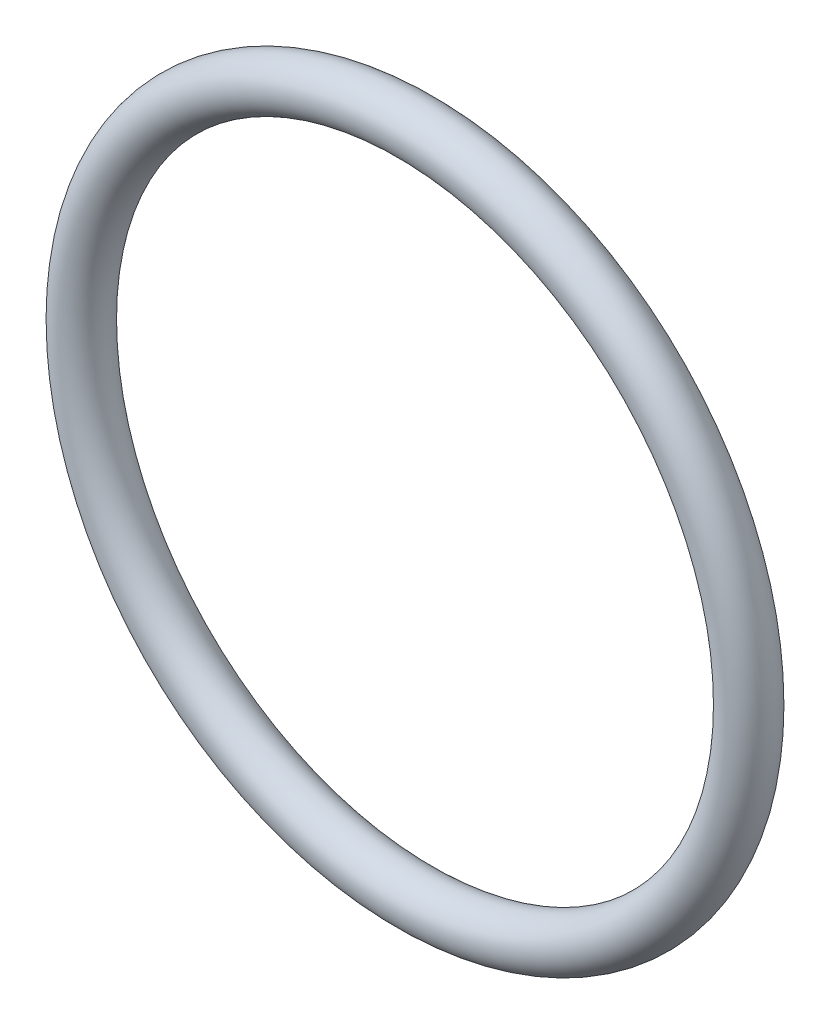
SolidWorks part; units mm, degrees
ref_plane "Front" through (0, 0, 0) normal (0, 0, 1) x (1, 0, 0)
ref_plane "Top" through (0, 0, 0) normal (0, 1, 0) x (1, 0, 0)
ref_plane "Right" through (0, 0, 0) normal (1, 0, 0) x (0, 0, -1)
sketch "Sketch1" plane through (0, 0, 0) normal (0, 0, 1) x (1, 0, 0)
  circle A0 centre (0, 0) radius 35.3
  dimension "d1" = 70.6
sketch "Sketch2" plane through (0, 0, 0) normal (0, 1, 0) x (1, 0, 0)
  circle A0 centre (-38.15, 0) radius 2.85
  point P2 (-35.3, 0)
  dimension "d2" = 5.7
sweep "Sweep1" add profiles "Sketch2" path "Sketch1"
ref_axis "Axis1" through (0, 0, -5.0798) along (0, 0, 1)
